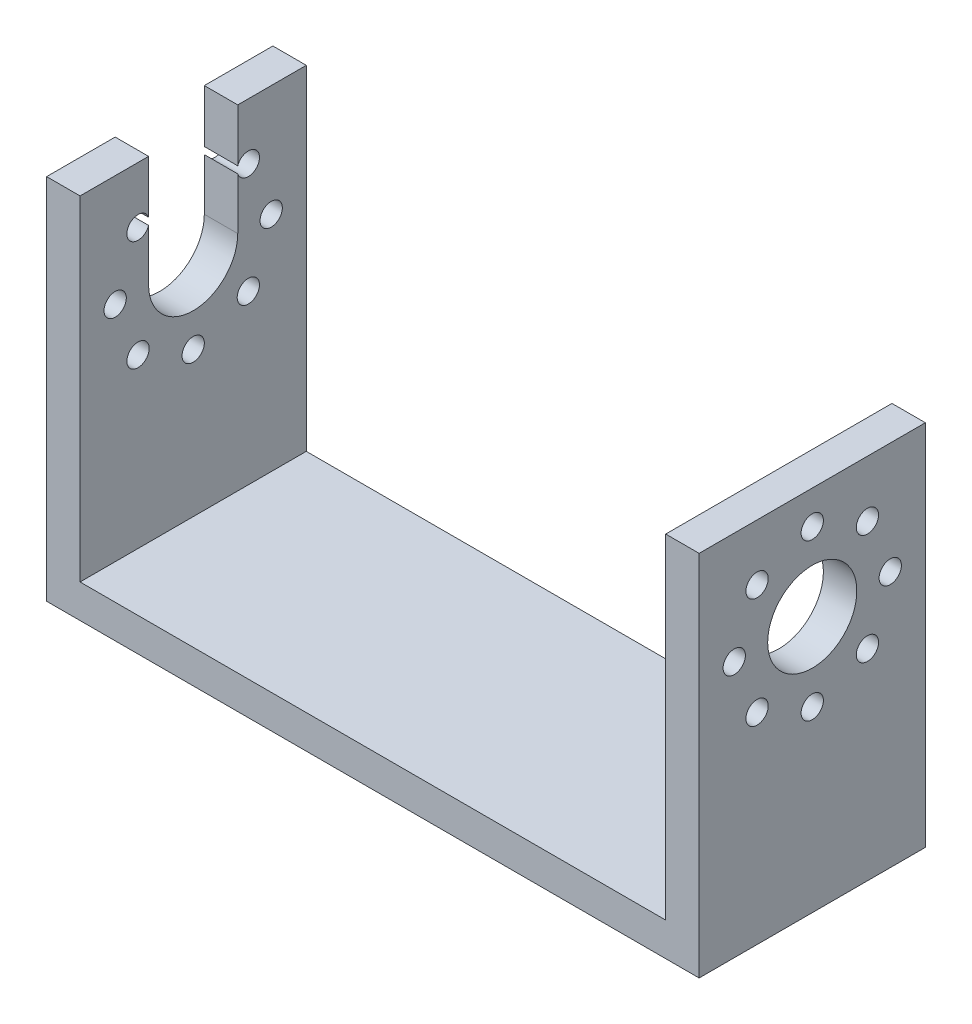
SolidWorks part; units mm, degrees
ref_plane "Front Plane" through (0, 0, 0) normal (0, 0, 1) x (1, 0, 0)
ref_plane "Top Plane" through (0, 0, 0) normal (0, 1, 0) x (1, 0, 0)
ref_plane "Right Plane" through (0, 0, 0) normal (1, 0, 0) x (0, 0, -1)
sketch "Sketch1" plane through (0, 0, 0) normal (0, 1, 0) x (1, 0, 0)
  line L1 (0, 0) -> (58.55, 0)
  line L2 (0, 0) -> (0, 20.3)
  line L3 (0, 20.3) -> (58.55, 20.3)
  line L4 (58.55, 0) -> (58.55, 20.3)
  dimension "D1" = 58.55
  dimension "D2" = 20.3
extrude "YawMount" add sketch "Sketch1" along normal blind 3
sketch "Sketch2" plane through (0, 3, 0) normal (0, 1, 0) x (1, 0, 0)
  line L0 (0, 0) -> (58.55, 0) construction
  line L1 (0, 20.3) -> (3, 20.3)
  line L2 (0, 20.3) -> (0, 0)
  line L3 (0, 0) -> (3, 0)
  line L4 (3, 20.3) -> (3, 0)
  line L6 (58.55, 20.3) -> (55.55, 20.3)
  line L7 (58.55, 20.3) -> (58.55, 0)
  line L8 (58.55, 0) -> (55.55, 0)
  line L9 (55.55, 20.3) -> (55.55, 0)
  dimension "D1" = 3
  dimension "D2" = 3
extrude "BodyConnectors" add sketch "Sketch2" along normal blind 30
sketch "Sketch3" plane through (58.55, 0, 0) normal (1, 0, 0) x (0, 0, -1)
  line L1 (0, 33) -> (20.3, 33) construction
  circle A9 centre (5.2003, 27.9497) radius 1
  circle A10 centre (10.15, 30) radius 1
  circle A11 centre (15.0997, 27.9497) radius 1
  circle A12 centre (17.15, 23) radius 1
  circle A13 centre (15.0997, 18.0503) radius 1
  circle A14 centre (10.15, 16) radius 1
  circle A15 centre (5.2003, 18.0503) radius 1
  circle A16 centre (3.15, 23) radius 1
  point P4 (10.15, 33)
  point P23 (10.15, 23)
  dimension "D1" = 2
  dimension "D2" = 20
  dimension "D3" = 7
extrude "Axle-Mounts" cut sketch "Sketch3" against normal up to surface (58.55 mm away) up to face at (0, 16.5, -10.15)
sketch "Sketch4" plane through (55.55, 0, 0) normal (-1, 0, 0) x (0, 0, 1)
  line L0 (0, 33) -> (-20.3, 33) construction
  circle A0 centre (-10.15, 23) radius 4
  circle A3 centre (-17.15, 23) radius 1 construction
  point P7 (-10.15, 33)
  dimension "D1" = 8
  dimension "D2" = 7
extrude "Axle-Counterbore" cut sketch "Sketch4" against normal up to surface and the other way up to surface up to face at (58.55, 30, -11.15) other way up to face at (0, 30, -11.15)
sketch "Sketch5" plane through (0, 33, 0) normal (0, 1, 0) x (1, 0, 0)
  line L0 (3, 0) -> (3, 20.3) construction
  line L1 (3, 14.15) -> (0, 14.15)
  line L2 (3, 14.15) -> (3, 6.15)
  line L3 (3, 6.15) -> (0, 6.15)
  line L4 (0, 14.15) -> (0, 6.15)
  line L5 (0, 20.3) -> (0, 0) construction
  point P8 (0, 10.15)
  point P9 (0, 10.15)
  dimension "D1" = 8
extrude "MotorAxleSlideGap" cut sketch "Sketch5" against normal blind 10
equation "\"srv_w\"= 40.43mm'width of Sain Smart SR319"
equation "\"D1@Sketch1\"=51.8mm + \"mnt_thick\"*2.25"
equation "\"srv_h\"= 40.61mm'height of Sain Smart SR319"
equation "\"srv_d\"= 20.3mm'depth of Sain Smart SR319"
equation "\"D2@Sketch1\"=\"srv_d\""
equation "\"mnt_thick\"= 3mm'thickness of bracket"
equation "\"D1@YawMount\" = \"mnt_thick\""
equation "\"D2@Sketch2\"=\"mnt_thick\""
equation "\"D1@Sketch2\"=\"mnt_thick\""
